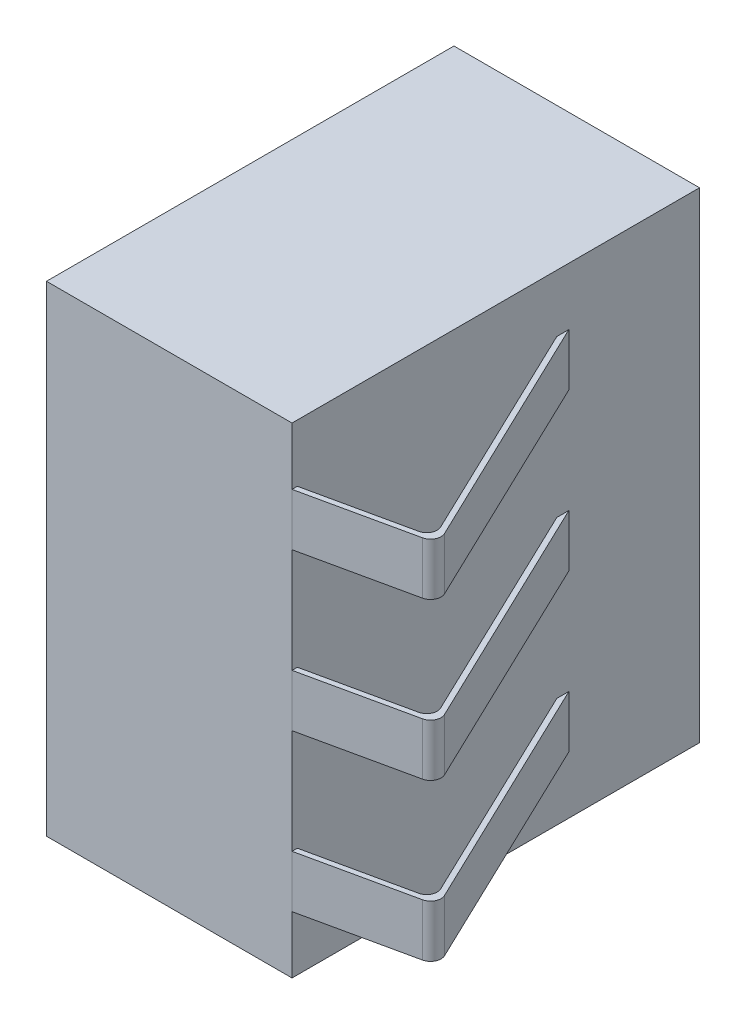
SolidWorks part; units mm, degrees
ref_plane "Front Plane" through (0, 0, 0) normal (0, 0, 1) x (1, 0, 0)
ref_plane "Top Plane" through (0, 0, 0) normal (0, 1, 0) x (1, 0, 0)
ref_plane "Right Plane" through (0, 0, 0) normal (1, 0, 0) x (0, 0, -1)
sketch "Sketch1" plane through (0, 0, 0) normal (0, 0, 1) x (1, 0, 0)
  line L1 (-2.35, -4.6) -> (2.35, -4.6)
  line L2 (-2.35, -4.6) -> (-2.35, 4.6)
  line L3 (-2.35, 4.6) -> (2.35, 4.6)
  line L4 (2.35, -4.6) -> (2.35, 4.6)
  line L5 (-2.35, -4.6) -> (2.35, 4.6) construction
  line L6 (-2.35, 4.6) -> (2.35, -4.6) construction
  point P0 (0, 0)
  dimension "D1" = 4.7
  dimension "D2" = 9.2
extrude "Boss-Extrude1" add sketch "Sketch1" along normal blind 7.8
sketch "Sketch2" plane through (0, 0, 0) normal (0, 1, 0) x (1, 0, 0)
  line L0 (2.35, -7.8) -> (4.65, -7.3)
  line L1 (2.35, -7.8) -> (2.35, 0) construction
  line L2 (4.65, -7.3) -> (2.35, -2.5)
  line L3 (2.35, -2.5) -> (2.35, -2.7314)
  line L4 (2.35, -2.7314) -> (4.5052, -7.2292)
  line L5 (4.5052, -7.2292) -> (2.35, -7.6977)
  line L6 (2.35, -7.6977) -> (2.35, -7.8)
  line L7 (4.5052, -7.2292) -> (4.5953, -7.1859) construction
  line L8 (4.5052, -7.2292) -> (4.5264, -7.3269) construction
  line L10 (2.35, 0) -> (-2.35, 0) construction
  line L11 (-2.35, -7.8) -> (-2.35, 0) construction
  line L12 (2.35, -7.8) -> (-2.35, -7.8) construction
  point P4 (2.35, -7.8)
  point P11 (4.6518, -7.4667)
  dimension "D1" = 0.1
  dimension "D2" = 2.5
  dimension "D3" = 7
  dimension "D4" = 0.5
extrude "Boss-Extrude2" add sketch "Sketch2" along normal mid plane 1
fillet "Fillet1" radius 0.2 1 edges at (4.5052, 0, 7.2292)
fillet "Fillet2" radius 0.2 1 edges at (4.65, 0, 7.3)
pattern_linear "LPattern2" count 2 spacing 3 along (0, -1, 0) count 2 spacing 3 along (0, 1, 0) of "Boss-Extrude2", "Fillet1", "Fillet2" pattern seed only yes
